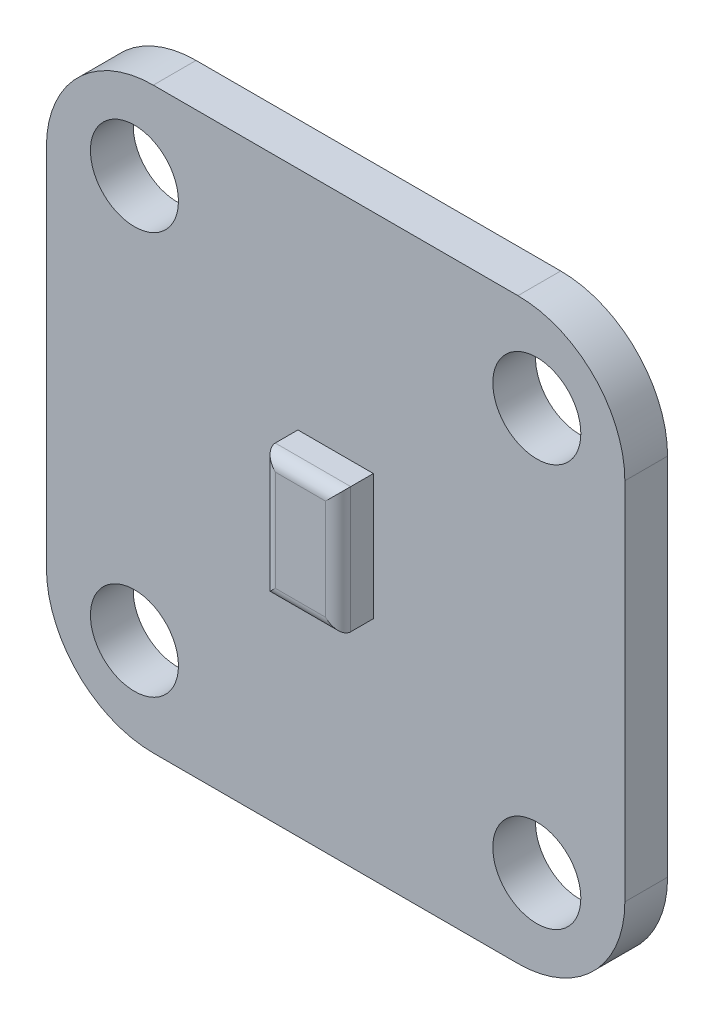
SolidWorks part; units mm, degrees
material "A-玻璃纤维"
ref_plane "前视基准面" through (0, 0, 0) normal (0, 0, 1) x (1, 0, 0)
ref_plane "上视基准面" through (0, 0, 0) normal (0, 1, 0) x (1, 0, 0)
ref_plane "右视基准面" through (0, 0, 0) normal (1, 0, 0) x (0, 0, -1)
sketch "草图2" plane through (0, 0, 0) normal (0, 0, 1) x (1, 0, 0)
  line L1 (-11.5, -11.5) -> (11.5, -11.5)
  line L2 (-11.5, -11.5) -> (-11.5, 11.5)
  line L3 (-11.5, 11.5) -> (11.5, 11.5)
  line L4 (11.5, -11.5) -> (11.5, 11.5)
  line L5 (-11.5, -11.5) -> (11.5, 11.5) construction
  line L6 (-11.5, 11.5) -> (11.5, -11.5) construction
  line L7 (-8, 8) -> (8, 8)
  line L8 (-8, 8) -> (-8, -8)
  line L9 (-8, -8) -> (8, -8)
  line L10 (8, 8) -> (8, -8)
  line L11 (-8, 8) -> (8, -8) construction
  line L12 (-8, -8) -> (8, 8) construction
  line L13 (-1.5, 2.5) -> (1.5, 2.5)
  line L14 (-1.5, 2.5) -> (-1.5, -2.5)
  line L15 (-1.5, -2.5) -> (1.5, -2.5)
  line L16 (1.5, 2.5) -> (1.5, -2.5)
  line L17 (-1.5, 2.5) -> (1.5, -2.5) construction
  line L18 (-1.5, -2.5) -> (1.5, 2.5) construction
  circle A0 centre (8, 8) radius 1.75
  circle A1 centre (-8, 8) radius 1.75
  circle A2 centre (8, -8) radius 1.75
  circle A3 centre (-8, -8) radius 1.75
  point P0 (0, 0)
  point P6 (0, 0)
  point P15 (0, 0)
  dimension "D4" = 3.5
  dimension "D5" = 3.5
  dimension "D6" = 3.5
  dimension "D7" = 3.5
  dimension "D1" = 23
  dimension "D2" = 23
  dimension "D3" = 16
  dimension "D8" = 3
  dimension "D9" = 5
extrude "凸台-拉伸1" add sketch "草图2" along normal blind 1.7 contours L1 L4 L3 L2 A3 L8 A1 L7 A0 L10 A2 L9 | A3 L9 A2 L10 A0 L7 A1 L8 L13 L16 L15 L14 | L16 L13 L14 L15 region at (-11.1747, 0, 0) region at (0, 7.7737, 0) region at (0, 0, 0)
extrude "凸台-拉伸2" add sketch "草图2<3>" along normal blind 3.1 contours L16 L15 L14 L13
sketch "草图2<3>" plane through (0, 0, 0) normal (0, 0, 1) x (1, 0, 0) same geometry as "草图2"
fillet "圆角2" radius 4.25 1 edges at (11.5, 11.5, 0.85)
fillet "圆角3" radius 4.25 1 edges at (-11.5, 11.5, 0.85)
fillet "圆角4" radius 4.25 1 edges at (-11.5, -11.5, 0.85)
fillet "圆角5" radius 4.25 1 edges at (11.5, -11.5, 0.85)
fillet "圆角6" radius 0.5 4 edges at (1.5, 0, 3.1) (0, -2.5, 3.1) (-1.5, 0, 3.1) (0, 2.5, 3.1)
